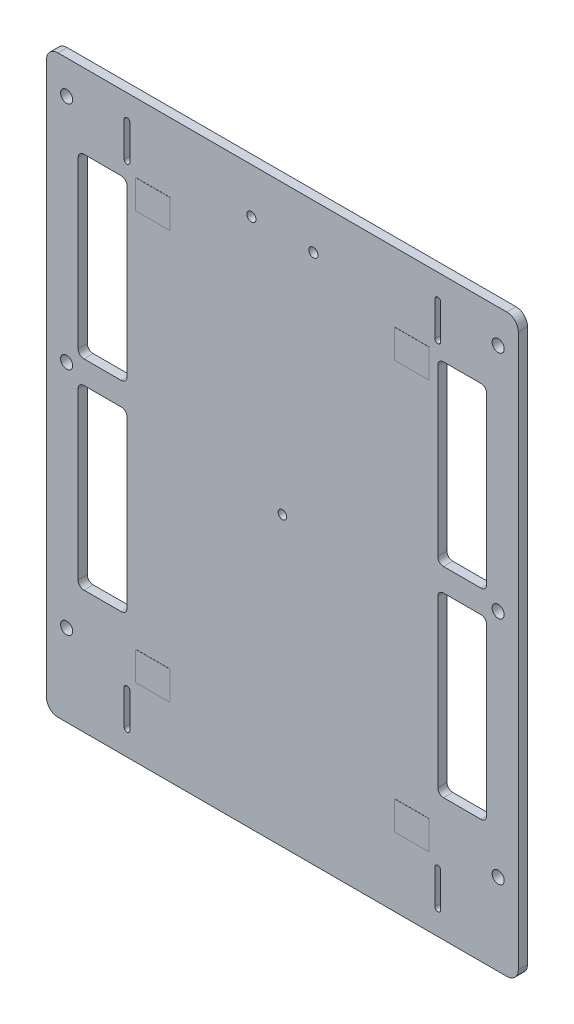
SolidWorks part; units mm, degrees
material "Oshpark board"
ref_plane "Front Plane" through (0, 0, 0) normal (0, 0, 1) x (1, 0, 0)
ref_plane "Top Plane" through (0, 0, 0) normal (0, 1, 0) x (1, 0, 0)
ref_plane "Right Plane" through (0, 0, 0) normal (1, 0, 0) x (0, 0, -1)
sketch "Sketch1" plane through (0, 0, 0) normal (0, 0, 1) x (1, 0, 0)
  line L1 (-39, -50) -> (39, -50)
  line L2 (-41, -48) -> (-41, 48)
  line L3 (-39, 50) -> (39, 50)
  line L4 (41, -48) -> (41, 48)
  line L5 (-41, -50) -> (41, 50) construction
  line L6 (-41, 50) -> (41, -50) construction
  arc A0 (-39, -50) -> (-41, -48) centre (-39, -48) cw
  arc A1 (39, -50) -> (41, -48) centre (39, -48) ccw
  arc A2 (39, 50) -> (41, 48) centre (39, 48) cw
  arc A3 (-41, 48) -> (-39, 50) centre (-39, 48) cw
  point P0 (0, 0)
  dimension "D3" = 2
  dimension "D1" = 100
  dimension "D2" = 82
extrude "Boss-Extrude1" add sketch "Sketch1" along normal blind 1.6
sketch "Sketch2" plane through (0, 0, 1.6) normal (0, 0, 1) x (1, 0, 0)
  line L0 (39, 50) -> (-39, 50) construction
  line L1 (-41, 48) -> (-41, -48) construction
  line L3 (-37.5, 44.2) -> (-37.5, 4.2) construction
  circle A0 centre (0, 0) radius 0.75
  circle A1 centre (-37.5, 44.2) radius 1.05
  circle A2 centre (37.5, 44.2) radius 1.05
  circle A3 centre (37.5, 4.2) radius 1.05
  circle A4 centre (37.5, -35.8) radius 1.05
  circle A5 centre (-37.5, 4.2) radius 1.05
  circle A6 centre (-37.5, -35.8) radius 1.05
  circle A7 centre (-5.38, 42.15) radius 0.8
  circle A8 centre (5.39, 42.15) radius 0.8
  dimension "D1" = 1.5
  dimension "D2" = 2.1
  dimension "D9" = 10.77
  dimension "D7" = 1.6
  dimension "D11" = 7.85
  dimension "D12" = 35.62
  dimension "D3" = 5.8
  dimension "D4" = 3.5
  dimension "D8" = 40
  dimension "D10" = 37.5
  dimension "D5" = 2
  dimension "D6" = 3
extrude "Cut-Extrude1" cut sketch "Sketch2" against normal through all
sketch "Sketch3" plane through (0, 0, 1.6) normal (0, 0, 1) x (1, 0, 0)
  line L0 (39, 50) -> (-39, 50) construction
  line L1 (-34.5, 37) -> (-28, 37)
  line L2 (-35.5, 36) -> (-35.5, 7.2)
  line L3 (-34.5, 6.2) -> (-28, 6.2)
  line L4 (-27, 36) -> (-27, 7.2)
  line L5 (-41, 48) -> (-41, -48) construction
  line L6 (28, 37) -> (34.5, 37)
  line L7 (27, 36) -> (27, 7.2)
  line L8 (35.5, 36) -> (35.5, 7.2)
  line L9 (28, 6.2) -> (34.5, 6.2)
  line L10 (28, 2.2) -> (34.5, 2.2)
  line L11 (27, 1.2) -> (27, -27.6)
  line L12 (35.5, 1.2) -> (35.5, -27.6)
  line L13 (28, -28.6) -> (34.5, -28.6)
  line L14 (-34.5, 2.2) -> (-28, 2.2)
  line L15 (-35.5, 1.2) -> (-35.5, -27.6)
  line L16 (-27, 1.2) -> (-27, -27.6)
  line L17 (-34.5, -28.6) -> (-28, -28.6)
  line L18 (-34.5, 37) -> (28, 37) construction
  line L19 (-39, -50) -> (39, -50) construction
  arc A0 (-35.5, 7.2) -> (-34.5, 6.2) centre (-34.5, 7.2) ccw
  arc A1 (-28, 6.2) -> (-27, 7.2) centre (-28, 7.2) ccw
  arc A2 (-28, 37) -> (-27, 36) centre (-28, 36) cw
  arc A3 (-34.5, 37) -> (-35.5, 36) centre (-34.5, 36) ccw
  arc A4 (28, 37) -> (27, 36) centre (28, 36) ccw
  arc A5 (34.5, 37) -> (35.5, 36) centre (34.5, 36) cw
  arc A6 (27, 7.2) -> (28, 6.2) centre (28, 7.2) ccw
  arc A7 (34.5, 6.2) -> (35.5, 7.2) centre (34.5, 7.2) ccw
  arc A8 (28, 2.2) -> (27, 1.2) centre (28, 1.2) ccw
  arc A9 (34.5, 2.2) -> (35.5, 1.2) centre (34.5, 1.2) cw
  arc A10 (27, -27.6) -> (28, -28.6) centre (28, -27.6) ccw
  arc A11 (34.5, -28.6) -> (35.5, -27.6) centre (34.5, -27.6) ccw
  arc A12 (-34.5, 2.2) -> (-35.5, 1.2) centre (-34.5, 1.2) ccw
  arc A13 (-28, 2.2) -> (-27, 1.2) centre (-28, 1.2) cw
  arc A14 (-35.5, -27.6) -> (-34.5, -28.6) centre (-34.5, -27.6) ccw
  arc A15 (-28, -28.6) -> (-27, -27.6) centre (-28, -27.6) ccw
  point P12 (-27, 6.2)
  point P15 (-27, 37)
  point P18 (-35.5, 37)
  dimension "D5" = 1
  dimension "D10" = 27
  dimension "D1" = 8.5
  dimension "D2" = 30.8
  dimension "D3" = 13
  dimension "D4" = 5.5
  dimension "D8" = 62.5
  dimension "D9" = 4
  dimension "D11" = 21.4
  dimension "D6" = 2
  dimension "D7" = 2
extrude "Cut-Extrude2" cut sketch "Sketch3" against normal through all
sketch "Sketch4" plane through (0, 0, 1.6) normal (0, 0, 1) x (1, 0, 0)
  line L0 (-27, 39.75) -> (-27, 45.75) construction
  line L1 (-27.5, 39.75) -> (-27.5, 45.75)
  line L2 (-26.5, 39.75) -> (-26.5, 45.75)
  line L3 (39, 50) -> (-39, 50) construction
  line L4 (-41, 48) -> (-41, -48) construction
  line L5 (27, 39.75) -> (27, 45.75) construction
  line L6 (26.5, 39.75) -> (26.5, 45.75)
  line L7 (27.5, 39.75) -> (27.5, 45.75)
  line L8 (27, -45.75) -> (27, -39.75) construction
  line L9 (26.5, -45.75) -> (26.5, -39.75)
  line L10 (27.5, -45.75) -> (27.5, -39.75)
  line L11 (-27, -45.75) -> (-27, -39.75) construction
  line L12 (-27.5, -45.75) -> (-27.5, -39.75)
  line L13 (-26.5, -45.75) -> (-26.5, -39.75)
  line L14 (-27, 39.75) -> (27, 39.75) construction
  line L15 (-39, -50) -> (39, -50) construction
  arc A0 (-27.5, 39.75) -> (-26.5, 39.75) centre (-27, 39.75) ccw
  arc A1 (-26.5, 45.75) -> (-27.5, 45.75) centre (-27, 45.75) ccw
  arc A2 (26.5, 39.75) -> (27.5, 39.75) centre (27, 39.75) ccw
  arc A3 (27.5, 45.75) -> (26.5, 45.75) centre (27, 45.75) ccw
  arc A4 (26.5, -45.75) -> (27.5, -45.75) centre (27, -45.75) ccw
  arc A5 (27.5, -39.75) -> (26.5, -39.75) centre (27, -39.75) ccw
  arc A6 (-27.5, -45.75) -> (-26.5, -45.75) centre (-27, -45.75) ccw
  arc A7 (-26.5, -39.75) -> (-27.5, -39.75) centre (-27, -39.75) ccw
  point P2 (-27, 42.75)
  point P16 (27, 42.75)
  point P23 (27, -42.75)
  point P30 (-27, -42.75)
  dimension "D1" = 4.25
  dimension "D2" = 13.5
  dimension "D3" = 1
  dimension "D4" = 6
  dimension "D7" = 54
  dimension "D8" = 14
  dimension "D9" = 4.25
  dimension "D10" = 4.25
  dimension "D5" = 2
  dimension "D6" = 2
extrude "Cut-Extrude3" cut sketch "Sketch4" against normal blind 1.6
sketch "Sketch5" plane through (0, 0, 1.6) normal (0, 0, 1) x (1, 0, 0)
  line L0 (-41, 48) -> (-41, -48) construction
  line L1 (-25.5, 38) -> (-19.5, 38)
  line L2 (-25.5, 38) -> (-25.5, 33)
  line L3 (-25.5, 33) -> (-19.5, 33)
  line L4 (-19.5, 38) -> (-19.5, 33)
  line L5 (39, 50) -> (-39, 50) construction
  line L6 (19.5, 38) -> (19.5, 33)
  line L7 (25.5, 38) -> (25.5, 33)
  line L8 (19.5, 33) -> (25.5, 33)
  line L9 (19.5, 38) -> (25.5, 38)
  line L10 (19.5, -33) -> (19.5, -38)
  line L11 (25.5, -33) -> (25.5, -38)
  line L12 (19.5, -38) -> (25.5, -38)
  line L13 (19.5, -33) -> (25.5, -33)
  line L14 (-25.5, -33) -> (-25.5, -38)
  line L15 (-19.5, -33) -> (-19.5, -38)
  line L16 (-25.5, -38) -> (-19.5, -38)
  line L17 (-25.5, -33) -> (-19.5, -33)
  line L18 (-25.5, 38) -> (19.5, 38) construction
  line L19 (-25.5, 38) -> (-25.5, -33) construction
  dimension "D1" = 5
  dimension "D2" = 6
  dimension "D3" = 15.5
  dimension "D4" = 12
  dimension "D7" = 45
  dimension "D8" = 71
  dimension "D5" = 2
  dimension "D6" = 2
extrude "Boss-Extrude2" add sketch "Sketch5" along normal blind 0.02
